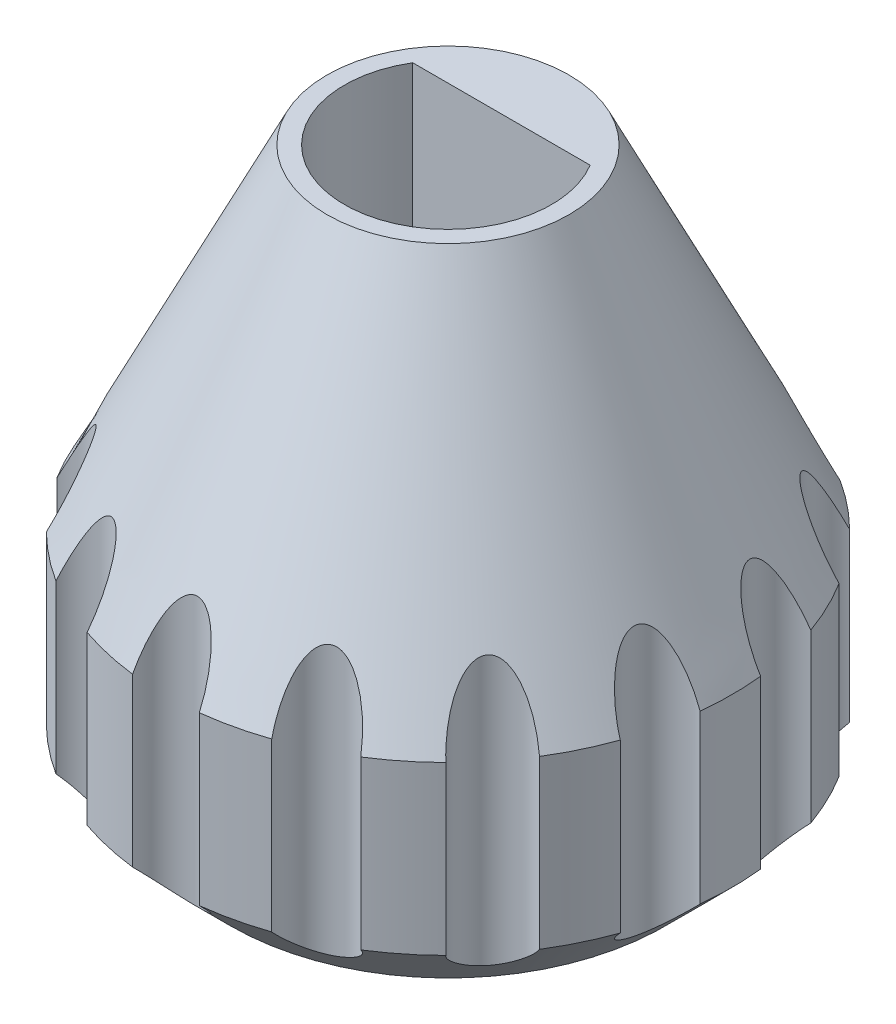
SolidWorks part; units mm, degrees
ref_plane "Front Plane" through (0, 0, 0) normal (0, 0, 1) x (1, 0, 0)
ref_plane "Top Plane" through (0, 0, 0) normal (0, 1, 0) x (1, 0, 0)
ref_plane "Right Plane" through (0, 0, 0) normal (1, 0, 0) x (0, 0, -1)
sketch "Sketch1" plane through (0, 0, 0) normal (0, 1, 0) x (1, 0, 0)
  circle A0 centre (0, 0) radius 8.5
  dimension "D1" = 17
extrude "Boss-Extrude1" add sketch "Sketch1" along normal blind 7
sketch "Sketch2" plane through (0, 7, 0) normal (0, 1, 0) x (1, 0, 0)
  circle A0 centre (0, 0) radius 3.5
  dimension "D1" = 7
extrude "Boss-Extrude2" add sketch "Sketch2" along normal blind 10
sketch "Sketch3" plane through (0, 17, 0) normal (0, 1, 0) x (1, 0, 0)
  line L0 (-2.6552, 1.6) -> (2.6552, 1.6)
  arc A0 (-2.6552, 1.6) -> (2.6552, 1.6) centre (0, 0) ccw
  dimension "D1" = 6.2
  dimension "D2" = 1.6
extrude "Cut-Extrude1" cut sketch "Sketch3" against normal blind 11
chamfer "Chamfer1" distance 5 angle 64 1 edges at (0, 7, 3.5) first distance on face at (0, 7, 3.5)
chamfer "Chamfer2" distance 2 angle 45 1 edges at (0, 0, 8.5)
sketch "Sketch4" plane through (0, 0, 0) normal (0, -1, 0) x (1, 0, 0)
  circle A0 centre (0, 8.5) radius 1
  circle A1 centre (0, 0) radius 8.5 construction
  circle A2 centre (3.688, 7.6582) radius 1
  circle A3 centre (6.6456, 5.2997) radius 1
  circle A4 centre (8.2869, 1.8914) radius 1
  circle A5 centre (8.2869, -1.8914) radius 1
  circle A6 centre (6.6456, -5.2997) radius 1
  circle A7 centre (3.688, -7.6582) radius 1
  circle A8 centre (0, -8.5) radius 1
  circle A9 centre (-3.688, -7.6582) radius 1
  circle A10 centre (-6.6456, -5.2997) radius 1
  circle A11 centre (-8.2869, -1.8914) radius 1
  circle A12 centre (-8.2869, 1.8914) radius 1
  circle A17 centre (-6.6456, 5.2997) radius 1
  circle A18 centre (-3.688, 7.6582) radius 1
  point P29 (0, 0)
  dimension "D1" = 2
  dimension "D2" = 14
extrude "Cut-Extrude2" cut sketch "Sketch4" against normal up to next
sketch "Sketch5" plane through (0, 6, 0) normal (0, 1, 0) x (1, 0, 0)
  line L2 (2.7111, 1.7) -> (-2.7111, 1.7)
  line L3 (2.7111, 1.7) -> (-2.7111, 1.7)
  arc A2 (-2.7111, 1.7) -> (2.7111, 1.7) centre (0, 0) ccw
  arc A3 (-2.7111, 1.7) -> (2.7111, 1.7) centre (0, 0) ccw
  dimension "D1" = 0.1
extrude "Cut-Extrude3" cut sketch "Sketch5" along normal blind 5
chamfer "Chamfer3" distance 0.1 angle 45 2 edges at (0, 11, -1.7) (0, 11, 3.2)
chamfer "Chamfer4" [suppressed] distance 1.5 angle 45
equation "\"2.5.000000mm\"=3"
